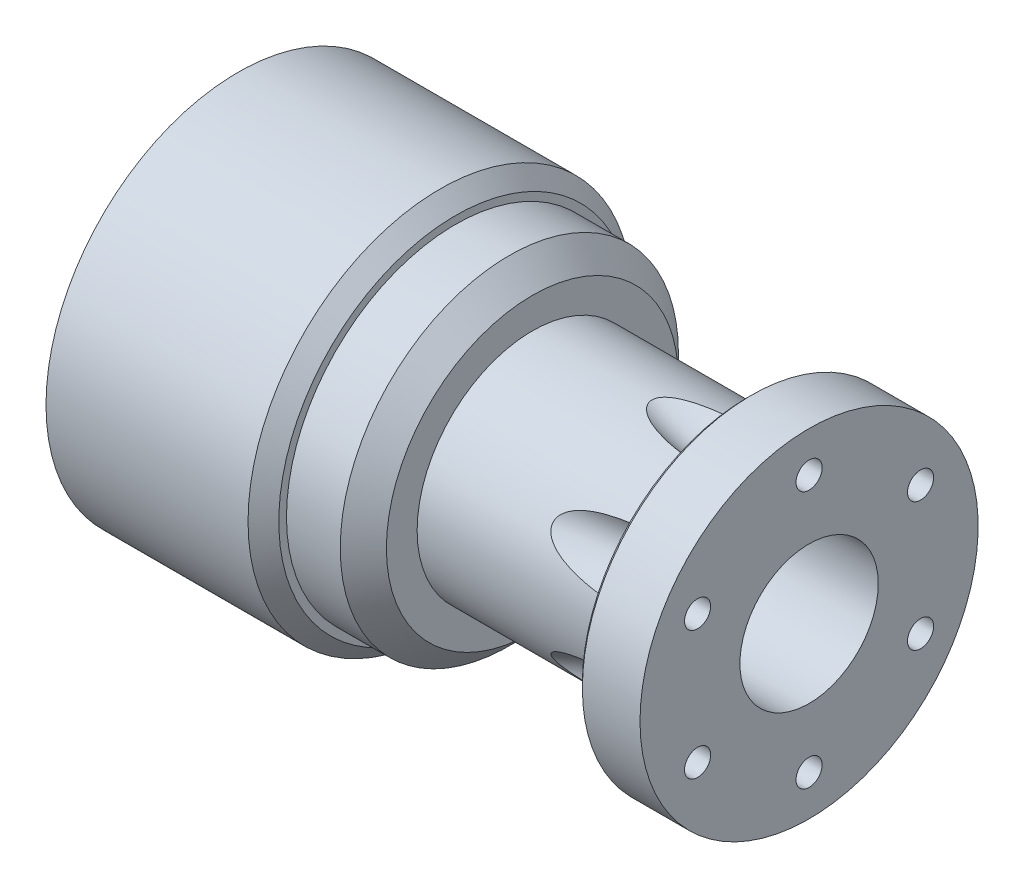
SolidWorks part; units mm, degrees
ref_plane "前视基准面" through (0, 0, 0) normal (0, 0, 1) x (1, 0, 0)
ref_plane "上视基准面" through (0, 0, 0) normal (0, 1, 0) x (1, 0, 0)
ref_plane "右视基准面" through (0, 0, 0) normal (1, 0, 0) x (0, 0, -1)
sketch "草图1" plane through (0, 0, 0) normal (0, 0, 1) x (1, 0, 0)
  line L0 (-39.2059, 0) -> (101.5198, 0) construction
  line L1 (0, 0) -> (0, 25)
  line L2 (0, 25) -> (28.29, 25)
  line L3 (28.29, 25) -> (28.29, 22)
  line L4 (28.29, 22) -> (38.29, 22)
  line L5 (38.29, 22) -> (38.29, 15)
  line L6 (38.29, 15) -> (66.29, 15)
  line L7 (66.29, 15) -> (66.29, 22)
  line L8 (66.29, 22) -> (74.29, 22)
  line L9 (74.29, 22) -> (74.29, 0)
  line L10 (74.29, 0) -> (0, 0)
  line L11 (0, 0) -> (0, 0.0744)
  dimension "D1" = 25
  dimension "D2" = 3
  dimension "D3" = 7
  dimension "D4" = 22
  dimension "D5" = 28.29
  dimension "D6" = 10
  dimension "D7" = 8
  dimension "D8" = 74.29
revolve "旋转1" add sketch "草图1" angle 360 about L0
sketch "草图2" plane through (74.29, 0, 0) normal (1, 0, 0) x (0, 0, -1)
  circle A0 centre (0, 0) radius 9
  dimension "D1" = 18
extrude "切除-拉伸1" cut sketch "草图2" against normal up to next
hole_wizard "打孔尺寸(%根据六角头螺)栓 全螺纹的类型1" positions "草图4" profile "草图3" counterbore size "M3" standard "GB" end condition through all
sketch "草图4" plane through (66.29, 0, 0) normal (-1, 0, 0) x (0, 0, 1)
  line L0 (0, 0) -> (0, 27.2919) construction
  circle A0 centre (0, 0) radius 16.75 construction
  point P0 (0, 16.75)
  dimension "D1" = 33.5
sketch "草图3" plane through (66.29, 16.75, 0) normal (0, 1, 0) x (0, 0, 1)
  line L0 (0, 0) -> (0, 8)
  line L1 (0, 8) -> (1.7, 8)
  line L3 (1.7, 8) -> (1.7, 5)
  line L4 (1.7, 5) -> (4.5, 5)
  line L5 (4.5, 5) -> (4.5, 0)
  line L7 (4.5, 0) -> (0, 0)
  line L11 (0, -6.35) -> (0, 107.95) construction
  dimension "通孔孔直径" = 3.4
  dimension "通孔孔深度" = 8
  dimension "柱形沉头孔直径" = 9
  dimension "柱形沉头孔深度" = 5
sketch "草图5" plane through (66.29, 0, 0) normal (-1, 0, 0) x (0, 0, 1)
  line L0 (0, 0) -> (0, 26.7173) construction
  circle A0 centre (0, 0) radius 16.75 construction
  circle A1 centre (0, 16.75) radius 4.5
  dimension "D1" = 9
  dimension "D2" = 33.5
sketch "草图6" plane through (0, 0, 0) normal (0, 0, 1) x (1, 0, 0)
  line L0 (66.29, 21.25) -> (66.29, 12.25) construction
  line L2 (66.29, 0) -> (66.29, 30.898) construction
  line L3 (66.29, 16.75) -> (66.29, -16.75) construction
  arc A0 (66.29, 16.75) -> (42.2169, 35.0056) centre (66.29, 41.75) cw
  dimension "D1" = 25
sweep "切除-扫描2" cut profiles "草图5" path "草图6"
ref_axis "基准轴1" through (0, 0, 0) along (1, 0, 0)
pattern_circular "阵列(圆周)1" count 6 over 360 about axis through (0, 0, 0) along (1, 0, 0) of "打孔尺寸(%根据六角头螺)栓 全螺纹的类型1", "切除-扫描2"
hole_wizard "M4 螺纹孔1" positions "草图10" profile "草图9" tap size "M4" standard "GB"
sketch "草图10" plane through (0, 0, 0) normal (-1, 0, 0) x (0, 0, 1)
  line L0 (0, 0) -> (0, 26.5532) construction
  circle A0 centre (0, 0) radius 17.5 construction
  point P0 (0, 17.5)
  dimension "D1" = 35
sketch "草图9" plane through (0, 17.5, 0) normal (0, 1, 0) x (0, 0, 1)
  line L0 (0, 0) -> (0, 7.5914)
  line L1 (0, 7.5914) -> (1.65, 6.6)
  line L2 (1.65, 6.6) -> (1.65, 0)
  line L5 (1.65, 0) -> (0, 0)
  line L10 (0, 7.5914) -> (-1.65, 6.6) construction
  line L11 (0, -6.35) -> (0, 107.95) construction
  dimension "螺纹孔钻头直径" = 3.3
  dimension "螺纹孔钻头深度" = 6.6
  dimension "导头角度" = 118
cosmetic thread "孔螺蚊线1" parameters "D1"=4.5, "D2"=4
pattern_circular "阵列(圆周)2" count 6 over 360 about axis through (0, 0, 0) along (1, 0, 0) of "M4 螺纹孔1"
chamfer "倒角1" distance 2 angle 45 1 edges at (28.29, 0, 25)
chamfer "倒角2" distance 3 angle 45 1 edges at (38.29, 0, 22)
chamfer "倒角3" distance 0.5 angle 45 1 edges at (66.29, 0, 22)
